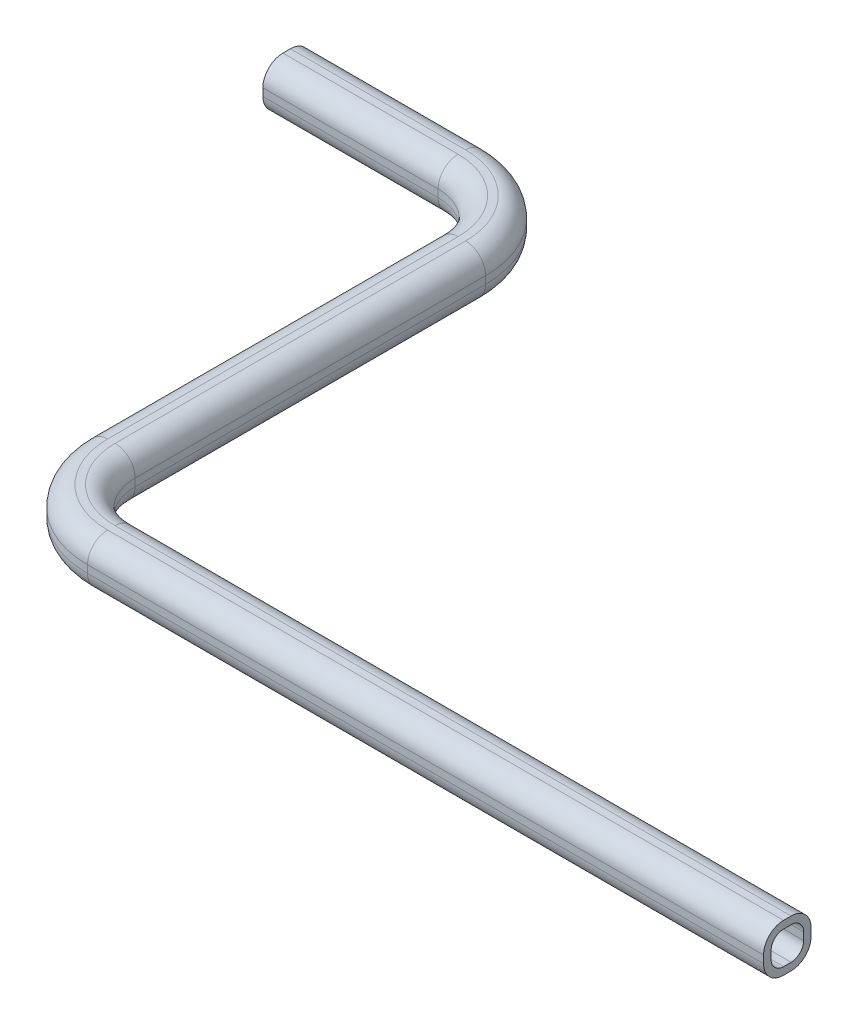
SolidWorks part; units mm, degrees
material "5052-H38, Rod (SS)"
ref_plane "Front Plane" through (0, 0, 0) normal (0, 0, 1) x (1, 0, 0)
ref_plane "Top Plane" through (0, 0, 0) normal (0, 1, 0) x (1, 0, 0)
ref_plane "Right Plane" through (0, 0, 0) normal (1, 0, 0) x (0, 0, -1)
sketch "Sketch1" plane through (0, 0, 0) normal (0, 1, 0) x (1, 0, 0)
  line L0 (0, 0) -> (-270, 0)
  line L2 (-300, 30) -> (-300, 170)
  line L3 (-330, 200) -> (-400, 200)
  arc A0 (-270, 0) -> (-300, 30) centre (-270, 30) cw
  arc A1 (-300, 170) -> (-330, 200) centre (-330, 170) ccw
  point P7 (-300, 0)
  point P11 (-300, 200)
  dimension "D3" = 200
  dimension "D4" = 30
  dimension "D1" = 300
  dimension "D2" = 100
sketch "Sketch2" plane through (0, 0, 0) normal (1, 0, 0) x (0, 0, -1)
  line L1 (-1.5, -6.5) -> (1.5, -6.5)
  line L2 (-6.5, -1.5) -> (-6.5, 1.5)
  line L3 (-1.5, 6.5) -> (1.5, 6.5)
  line L4 (6.5, -1.5) -> (6.5, 1.5)
  line L5 (-6.5, -6.5) -> (6.5, 6.5) construction
  line L6 (-6.5, 6.5) -> (6.5, -6.5) construction
  arc A0 (-1.5, 6.5) -> (-6.5, 1.5) centre (-1.5, 1.5) ccw
  arc A1 (-6.5, -1.5) -> (-1.5, -6.5) centre (-1.5, -1.5) ccw
  arc A2 (1.5, -6.5) -> (6.5, -1.5) centre (1.5, -1.5) ccw
  arc A3 (6.5, 1.5) -> (1.5, 6.5) centre (1.5, 1.5) ccw
  point P0 (0, 0)
  dimension "D3" = 5
  dimension "D1" = 13
  dimension "D2" = 13
sweep "Sweep-Thin1" add profiles "Sketch2" path "Sketch1" parameters "D1"=3
